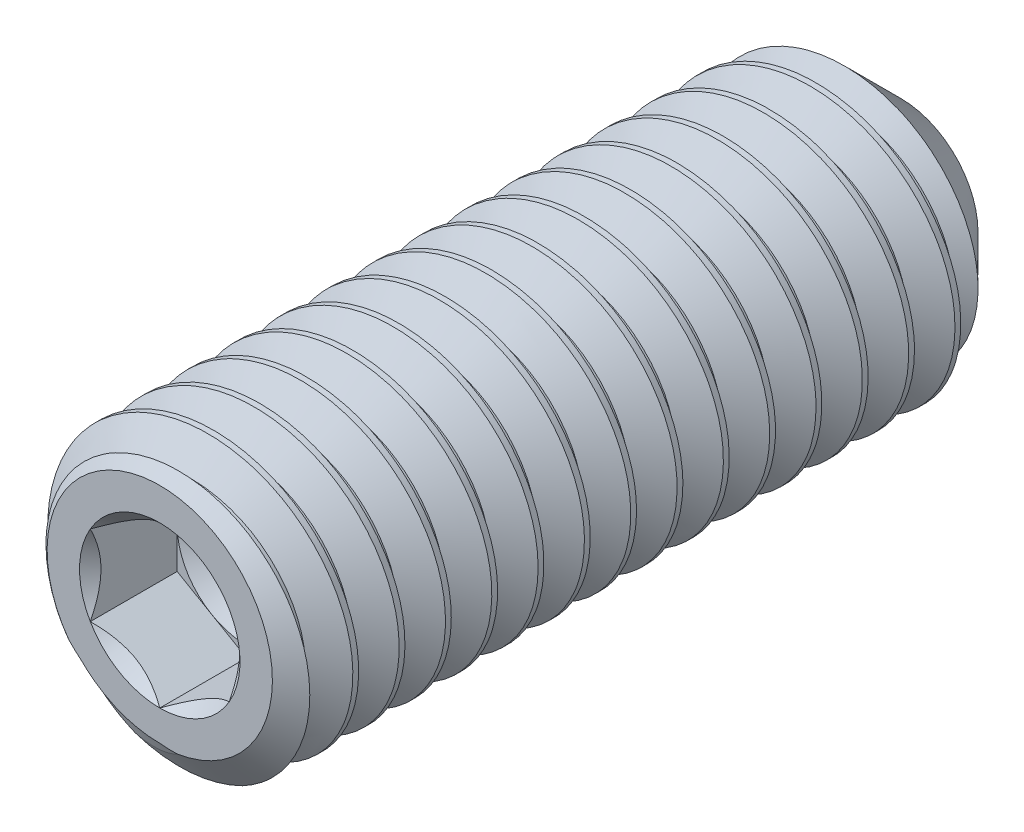
SolidWorks part; units mm, degrees
ref_plane "Front" through (0, 0, 0) normal (0, 0, 1) x (1, 0, 0)
ref_plane "Top" through (0, 0, 0) normal (0, 1, 0) x (1, 0, 0)
ref_plane "Right" through (0, 0, 0) normal (1, 0, 0) x (0, 0, -1)
sketch "Sketch22" plane through (0, 0, 0) normal (1, 0, 0) x (0, 0, -1)
  line L0 (-5.9528, 0) -> (-5.9528, 1.9304)
  line L1 (-5.9528, 1.9304) -> (-5.6148, 2.413)
  line L2 (-5.6148, 2.413) -> (5.6565, 2.413)
  line L3 (5.6565, 2.413) -> (6.7472, 1.3222)
  line L4 (6.7472, 1.3222) -> (5.9528, 0)
  line L5 (5.9528, 0) -> (-5.9528, 0)
  line L6 (5.9528, 0) -> (6.7472, 0) construction
  line L7 (6.7472, 0) -> (6.7472, 1.3222) construction
  line L8 (6.7472, -1.3222) -> (5.9528, 0) construction
  line L9 (-5.6148, -2.413) -> (5.6565, -2.413) construction
  dimension "Dia" = 4.826
  dimension "Length" = 12.7
  dimension "D3" = 35
  dimension "D5" = 118
  dimension "D6" = 45
  dimension "D7" = 3.8608
revolve "Revolve1" add sketch "Sketch22" angle 360 about L6
ref_plane "Plane1" through (0, 0, -6.7472) normal (0, 0, 1) x (1, 0, 0)
sketch "Sketch27" plane through (0, 0, -6.7472) normal (0, 0, 1) x (1, 0, 0)
  circle A0 centre (0, 0) radius 2.413 construction
  circle A1 centre (0, 0) radius 2.413
curve "Helix/Spiral1" pitch 0.7937 height 13.4937 radius 2.413 centre (0, 0, -6.7472) axis (0, 0, 1) start towards (0, 1, 0)
sketch "Sketch28" plane through (0, 0, 0) normal (1, 0, 0) x (0, 0, -1)
  line L0 (6.7472, 2.413) -> (7.4418, 2.413)
  line L1 (7.4418, 2.413) -> (7.1441, 1.8974)
  line L2 (7.1441, 1.8974) -> (7.0449, 1.8974)
  line L3 (7.0449, 1.8974) -> (6.7472, 2.413)
  line L4 (6.8961, 2.1552) -> (7.2929, 2.1552) construction
  line L6 (-5.6148, 2.413) -> (5.6565, 2.413) construction
  line L7 (6.7472, 2.6543) -> (6.7472, -2.6543) construction
  dimension "D1" = 0.0992
  dimension "D3" = 60
  dimension "D2" = 0.3969
sweep "Cut-Sweep2" cut profiles "Sketch28" path "Helix/Spiral1"
sketch "Sketch23" plane through (0, 0, 5.9528) normal (0, 0, 1) x (1, 0, 0)
  line L1 (0, 1.3748) -> (-1.1906, 0.6874)
  line L2 (-1.1906, 0.6874) -> (-1.1906, -0.6874)
  line L3 (-1.1906, -0.6874) -> (0, -1.3748)
  line L4 (0, -1.3748) -> (1.1906, -0.6874)
  line L5 (1.1906, -0.6874) -> (1.1906, 0.6874)
  line L6 (1.1906, 0.6874) -> (0, 1.3748)
  circle A0 centre (0, 0) radius 1.1906 construction
  dimension "Hex" = 2.3813
extrude "Cut-Extrude10" cut sketch "Sketch23" against normal blind 1.4883
sketch "Sketch24" plane through (0, 0, 5.9528) normal (0, 0, 1) x (1, 0, 0)
  circle A0 centre (0, 0) radius 1.3748
extrude "Cut-Extrude11" cut sketch "Sketch24" against normal through all draft 45
sketch "Sketch26" plane through (0, 0, 4.4645) normal (0, 0, 1) x (1, 0, 0)
  circle A0 centre (0, 0) radius 1.1906 construction
  circle A1 centre (0, 0) radius 1.1906
extrude "Cut-Extrude12" cut sketch "Sketch26" against normal through all draft 60
sketch "Sketch30" plane through (0, 0, 0) normal (1, 0, 0) x (0, 0, -1)
  line L0 (-5.6148, 2.413) -> (5.6565, 2.413) construction
  line L1 (-5.9528, 0) -> (-5.9528, 1.9304) construction
  line L2 (6.7472, 0) -> (6.7472, 1.3222) construction
  line L3 (-5.6148, -2.413) -> (5.6565, -2.413) construction
  point P0 (-5.9528, 2.413)
  point P1 (6.7472, 2.413)
  point P2 (6.7472, -2.413)
  point P11 (3.9691, -2.413)
  dimension "D1" = 2.7781
sketch "Sketch31" plane through (0, 0, 0) normal (1, 0, 0) x (0, 0, -1)
  line L2 (5.9528, 0) -> (6.7472, -1.3222)
  line L3 (6.7472, 1.3222) -> (5.9528, 0)
equation "\"D7@Sketch22\"=\"Dia@Sketch22\"*.8"
equation "\"D1@Sketch28\" = \"D4@Helix/Spiral1\" * .125"
equation "\"D3@Helix/Spiral1\" = \"Length@Sketch22\" + \"D4@Helix/Spiral1\""
equation "\"D1@Sketch30\" = \"D4@Helix/Spiral1\" * 3.5"
equation "\"hex Depth@Cut-Extrude10\" = \"Hex@Sketch23\" * .625"
equation "\"D2@Sketch28\" = \"D4@Helix/Spiral1\" * .5"
